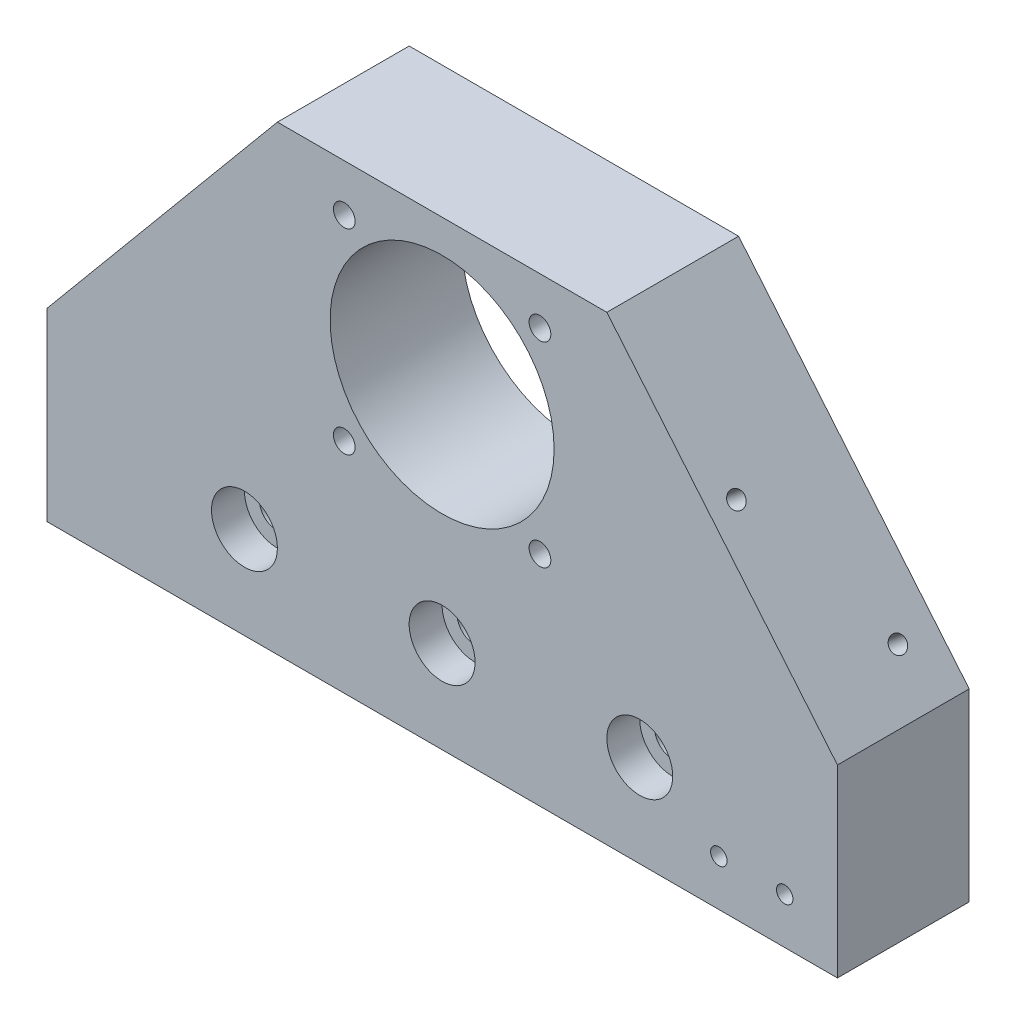
SolidWorks part; units mm, degrees
ref_plane "Front Plane" through (0, 0, 0) normal (0, 0, 1) x (1, 0, 0)
ref_plane "Top Plane" through (0, 0, 0) normal (0, 1, 0) x (1, 0, 0)
ref_plane "Right Plane" through (0, 0, 0) normal (1, 0, 0) x (0, 0, -1)
sketch "Sketch1" plane through (0, 0, 0) normal (0, 0, 1) x (1, 0, 0)
  line L0 (60, 0) -> (-60, 0)
  line L1 (-60, 0) -> (-60, 28)
  line L2 (-60, 28) -> (-25, 70)
  line L3 (-25, 70) -> (25, 70)
  line L4 (0, 0) -> (0, 70) construction
  line L5 (60, 28) -> (25, 70)
  line L6 (60, 0) -> (60, 28)
  dimension "D1" = 120
  dimension "D2" = 28
  dimension "D3" = 50
  dimension "D4" = 70
extrude "Boss-Extrude1" add sketch "Sketch1" along normal blind 20
sketch "Sketch2" plane through (0, 0, 20) normal (0, 0, 1) x (1, 0, 0)
  line L0 (0, 0) -> (0, 70) construction
  line L1 (-60, 0) -> (60, 0) construction
  line L2 (25, 70) -> (-25, 70) construction
  line L3 (-60, 14) -> (60, 14) construction
  line L4 (-60, 28) -> (-60, 0) construction
  line L5 (60, 0) -> (60, 28) construction
  point P12 (0, 14)
  point P13 (-30, 14)
  point P14 (30, 14)
  point P15 (0, 48)
  dimension "D1" = 30
hole_wizard "CBORE for M5 SHCS1" positions "3DSketch1" profile "Sketch3" counterbore size "M5" standard "ANSI Metric" end condition through all
sketch3d "3DSketch1"
  point P0 (-30, 14, 20)
  point P3 (0, 14, 20)
  point P6 (30, 14, 20)
sketch "Sketch3" plane through (-30, 14, 20) normal (1, 0, 0) x (0, -1, 0)
  line L0 (0, 0) -> (0, 20)
  line L1 (0, 20) -> (2.75, 20)
  line L3 (2.75, 20) -> (2.75, 5)
  line L4 (2.75, 5) -> (5, 5)
  line L5 (5, 5) -> (5, 0)
  line L7 (5, 0) -> (0, 0)
  line L11 (0, -6.35) -> (0, 107.95) construction
  dimension "Thru Hole Dia." = 5.5
  dimension "Thru Hole Depth" = 20
  dimension "C'Bore Dia." = 10
  dimension "C'Bore Depth" = 5
sketch "Sketch4" plane through (0, 0, 20) normal (0, 0, 1) x (1, 0, 0)
  circle A0 centre (0, 48) radius 17
  dimension "D1" = 34
extrude "Cut-Extrude1" cut sketch "Sketch4" against normal through all
sketch "Sketch5" plane through (0, 0, 20) normal (0, 0, 1) x (1, 0, 0)
  point P0 (14.8492, 33.1508)
  point P1 (-14.8492, 33.1508)
  point P2 (-14.8492, 62.8492)
  point P3 (14.8492, 62.8492)
hole_wizard "M4 Tapped Hole1" positions "3DSketch3" profile "Sketch7" tap size "M4" standard "ISO" end condition through all
sketch3d "3DSketch3"
  point P0 (-14.8492, 62.8492, 20)
  point P3 (14.8492, 62.8492, 20)
  point P6 (14.8492, 33.1508, 20)
  point P9 (-14.8492, 33.1508, 20)
sketch "Sketch7" plane through (-14.8492, 62.8492, 20) normal (1, 0, 0) x (0, -1, 0)
  line L0 (0, 0) -> (0, 20)
  line L1 (0, 20) -> (1.65, 20)
  line L2 (1.65, 20) -> (1.65, 0)
  line L5 (1.65, 0) -> (0, 0)
  line L11 (0, -6.35) -> (0, 107.95) construction
  dimension "Thread Major Dia." = 3.3
  dimension "Thru Tap Drill Depth" = 20
sketch "Sketch8" plane through (0, 0, 0) normal (0, -1, 0) x (1, 0, 0)
  line L0 (-20, 18.72) -> (-20, 0) construction
  line L1 (-60, 0) -> (60, 0) construction
  line L2 (20, 18.72) -> (20, 0) construction
  line L3 (-60, 10) -> (60, 10) construction
  line L4 (-60, 20) -> (-60, 0) construction
  line L5 (60, 20) -> (60, 0) construction
  line L6 (0, 0) -> (0, 20) construction
  point P12 (-20, 10)
  point P13 (20, 10)
  dimension "D1" = 20
  dimension "D2" = 20
hole_wizard "M4 Tapped Hole2" positions "Sketch10" profile "Sketch11" tap size "M4" standard "ISO"
sketch "Sketch10" plane through (0, 0, 0) normal (0, -1, 0) x (-1, 0, 0)
  point P0 (20, -10)
  point P3 (-20, -10)
sketch "Sketch11" plane through (-20, 0, 10) normal (1, 0, 0) x (0, 0, -1)
  line L0 (0, 0) -> (0, 15.9914)
  line L1 (0, 15.9914) -> (1.65, 15)
  line L2 (1.65, 15) -> (1.65, 0)
  line L5 (1.65, 0) -> (0, 0)
  line L10 (0, 15.9914) -> (-1.65, 15) construction
  line L11 (0, -6.35) -> (0, 107.95) construction
  dimension "Tap Drill Dia." = 3.3
  dimension "Tap Drill Depth" = 15
  dimension "Drill Angle" = 118
sketch "Sketch12" plane through (0, 0, 20) normal (0, 0, 1) x (1, 0, 0)
  line L0 (60, 0) -> (60, 28) construction
  line L2 (47, 0) -> (47, 14) construction
  line L3 (52, 7) -> (42, 7) construction
  line L5 (-60, 0) -> (60, 0) construction
  line L6 (-60, 14) -> (60, 14) construction
  point P9 (42, 7)
  point P10 (52, 7)
  dimension "D1" = 13
  dimension "D2" = 7
  dimension "D3" = 5
hole_wizard "M3 Tapped Hole1" positions "3DSketch5" profile "Sketch14" tap size "M3" standard "ISO"
sketch3d "3DSketch5"
  point P0 (42, 7, 20)
  point P3 (52, 7, 20)
sketch "Sketch14" plane through (42, 7, 20) normal (1, 0, 0) x (0, -1, 0)
  line L0 (0, 0) -> (0, 8.2511)
  line L1 (0, 8.2511) -> (1.25, 7.5)
  line L2 (1.25, 7.5) -> (1.25, 0)
  line L5 (1.25, 0) -> (0, 0)
  line L10 (0, 8.2511) -> (-1.25, 7.5) construction
  line L11 (0, -6.35) -> (0, 107.95) construction
  dimension "Tap Drill Dia." = 2.5
  dimension "Tap Drill Depth" = 7.5
  dimension "Drill Angle" = 118
sketch "Sketch15" plane through (49.1803, 40.9836, 0) normal (0.7682, 0.6402, 0) x (0, 0, -1)
  line L1 (-20, 0) -> (-20, 53.7755) construction
  line L2 (-20, -16.9009) -> (0, -16.9009) construction
  point P0 (-5.7, -8.9009)
  point P1 (-16, 13.2991)
  dimension "D1" = 22.2
  dimension "D2" = 10.3
  dimension "D3" = 4
  dimension "D4" = 8
hole_wizard "M3 Tapped Hole2" positions "Sketch17" profile "Sketch16" tap size "M3" standard "ISO"
sketch "Sketch17" plane through (49.1803, 40.9836, 0) normal (0.7682, 0.6402, 0) x (0, 0, -1)
  point P0 (-16, 13.2991)
  point P3 (-5.7, -8.9009)
sketch "Sketch16" plane through (40.6664, 51.2003, 16) normal (0, 0, 1) x (-0.6402, 0.7682, 0)
  line L0 (0, 0) -> (0, 12.2511)
  line L1 (0, 12.2511) -> (1.25, 11.5)
  line L2 (1.25, 11.5) -> (1.25, 0)
  line L5 (1.25, 0) -> (0, 0)
  line L10 (0, 12.2511) -> (-1.25, 11.5) construction
  line L11 (0, -6.35) -> (0, 107.95) construction
  dimension "Tap Drill Dia." = 2.5
  dimension "Tap Drill Depth" = 11.5
  dimension "Drill Angle" = 118
